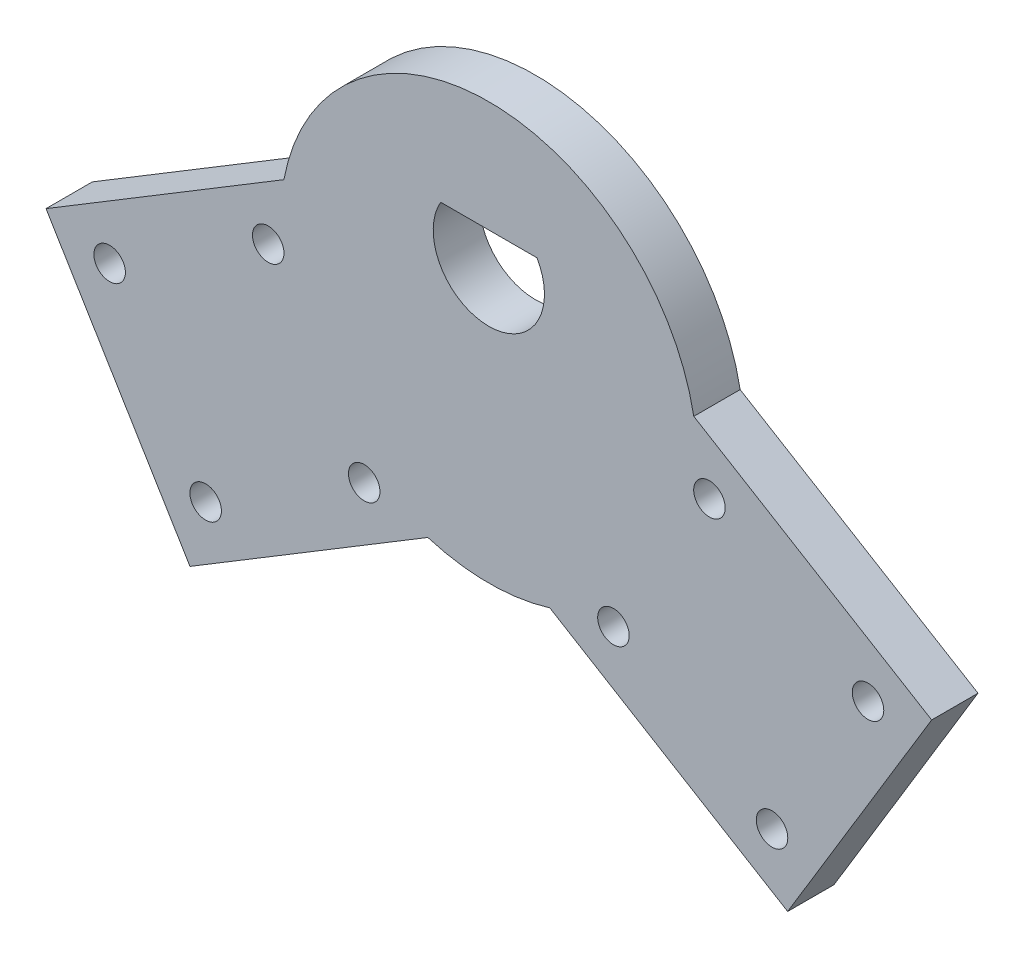
SolidWorks part; units mm, degrees
material "PLA 15%"
ref_plane "Front Plane" through (0, 0, 0) normal (0, 0, 1) x (1, 0, 0)
ref_plane "Top Plane" through (0, 0, 0) normal (0, 1, 0) x (1, 0, 0)
ref_plane "Right Plane" through (0, 0, 0) normal (1, 0, 0) x (0, 0, -1)
sketch "Sketch2" plane through (0, 0, 0) normal (0, 0, 1) x (1, 0, 0)
  line L8 (0, 0) -> (0, -22.5) construction
  line L9 (0, 0) -> (6.5784, -21.5169) construction
  line L10 (0, 0) -> (-6.5784, -21.5169) construction
  line L11 (6.5784, -21.5169) -> (22.1146, 4.1469) construction
  line L12 (6.5784, -21.5169) -> (32.2421, -37.053)
  line L13 (22.1146, 4.1469) -> (47.7783, -11.3893)
  line L14 (32.2421, -37.053) -> (47.7783, -11.3893)
  line L15 (-6.5784, -21.5169) -> (-22.1146, 4.1469) construction
  line L16 (-6.5784, -21.5169) -> (-32.2421, -37.053)
  line L17 (-22.1146, 4.1469) -> (-47.7783, -11.3893)
  line L18 (-32.2421, -37.053) -> (-47.7783, -11.3893)
  line L19 (-15.6807, -16.1358) -> (-21.5667, -6.4129) construction
  line L20 (-23.8025, -2.7198) -> (-40.9116, -13.0772) construction
  line L21 (-30.5542, -30.1864) -> (-40.9116, -13.0772) construction
  line L22 (-13.445, -19.8289) -> (-30.5542, -30.1864) construction
  line L23 (13.445, -19.8289) -> (15.6807, -16.1358) construction
  line L24 (23.8025, -2.7198) -> (40.9116, -13.0772) construction
  line L25 (30.5542, -30.1864) -> (40.9116, -13.0772) construction
  line L26 (13.445, -19.8289) -> (30.5542, -30.1864) construction
  line L27 (-21.5667, -6.4129) -> (-23.8025, -2.7198) construction
  line L28 (-13.445, -19.8289) -> (-23.8025, -2.7198) construction
  line L29 (-13.445, -19.8289) -> (-15.6807, -16.1358) construction
  line L30 (15.6807, -16.1358) -> (21.5667, -6.4129) construction
  line L31 (21.5667, -6.4129) -> (23.8025, -2.7198) construction
  line L32 (13.445, -19.8289) -> (23.8025, -2.7198) construction
  line L33 (0, 22.5) -> (0, -22.5) construction
  line L34 (5.1962, 10.5) -> (-5.1962, 10.5)
  arc A0 (-21.5667, -6.4129) -> (-15.6807, -16.1358) centre (0, 0) ccw construction
  arc A1 (-22.1146, 4.1469) -> (-21.5667, -6.4129) centre (0, 0) ccw construction
  arc A2 (-15.6807, -16.1358) -> (-6.5784, -21.5169) centre (0, 0) ccw construction
  arc A3 (-6.5784, -21.5169) -> (6.5784, -21.5169) centre (0, 0) ccw
  arc A4 (15.6807, -16.1358) -> (21.5667, -6.4129) centre (0, 0) ccw construction
  arc A5 (22.1146, 4.1469) -> (-22.1146, 4.1469) centre (0, 0) ccw
  arc A6 (21.5667, -6.4129) -> (22.1146, 4.1469) centre (0, 0) ccw construction
  arc A7 (6.5784, -21.5169) -> (15.6807, -16.1358) centre (0, 0) ccw construction
  arc A8 (-5.1962, 10.5) -> (5.1962, 10.5) centre (0, 7.5) ccw
  arc A9 (-5.1962, 10.5) -> (5.1962, 10.5) centre (0, 7.5) cw construction
  point P28 (0, 13.5)
  dimension "D5" = 45
  dimension "D10" = 6
  dimension "D1" = 17
  dimension "D2" = 17
  dimension "D3" = 30
  dimension "D4" = 30
  dimension "D6" = 30
  dimension "D7" = 30
  dimension "D9" = 30
  dimension "D11" = 3
  dimension "D8" = 5
extrude "Boss-Extrude1" add sketch "Sketch2" along normal blind 5 contours L13 A5 L17 L18 L16 A3 L12 L14 A8 L34
hole_wizard "M3 Clearance Hole1" positions "Sketch5" profile "Sketch6" hole size "M3" standard "ANSI Metric" end condition through all
sketch "Sketch5" plane through (0, 0, 5) normal (0, 0, 1) x (1, 0, 0)
  point P0 (-40.9116, -13.0772)
  point P3 (-23.8025, -2.7198)
  point P6 (-13.445, -19.8289)
  point P9 (-30.5542, -30.1864)
  point P12 (13.445, -19.8289)
  point P15 (23.8025, -2.7198)
  point P18 (40.9116, -13.0772)
  point P21 (30.5542, -30.1864)
sketch "Sketch6" plane through (-40.9116, -13.0772, 5) normal (1, 0, 0) x (0, -1, 0)
  line L0 (0, 0) -> (0, 5)
  line L1 (0, 5) -> (1.7, 5)
  line L2 (1.7, 5) -> (1.7, 0)
  line L5 (1.7, 0) -> (0, 0)
  line L11 (0, -6.35) -> (0, 107.95) construction
  dimension "Thru Hole Dia." = 3.4
  dimension "Thru Hole Depth" = 5
equation "\"dshaftdistance\"= 0.25"
